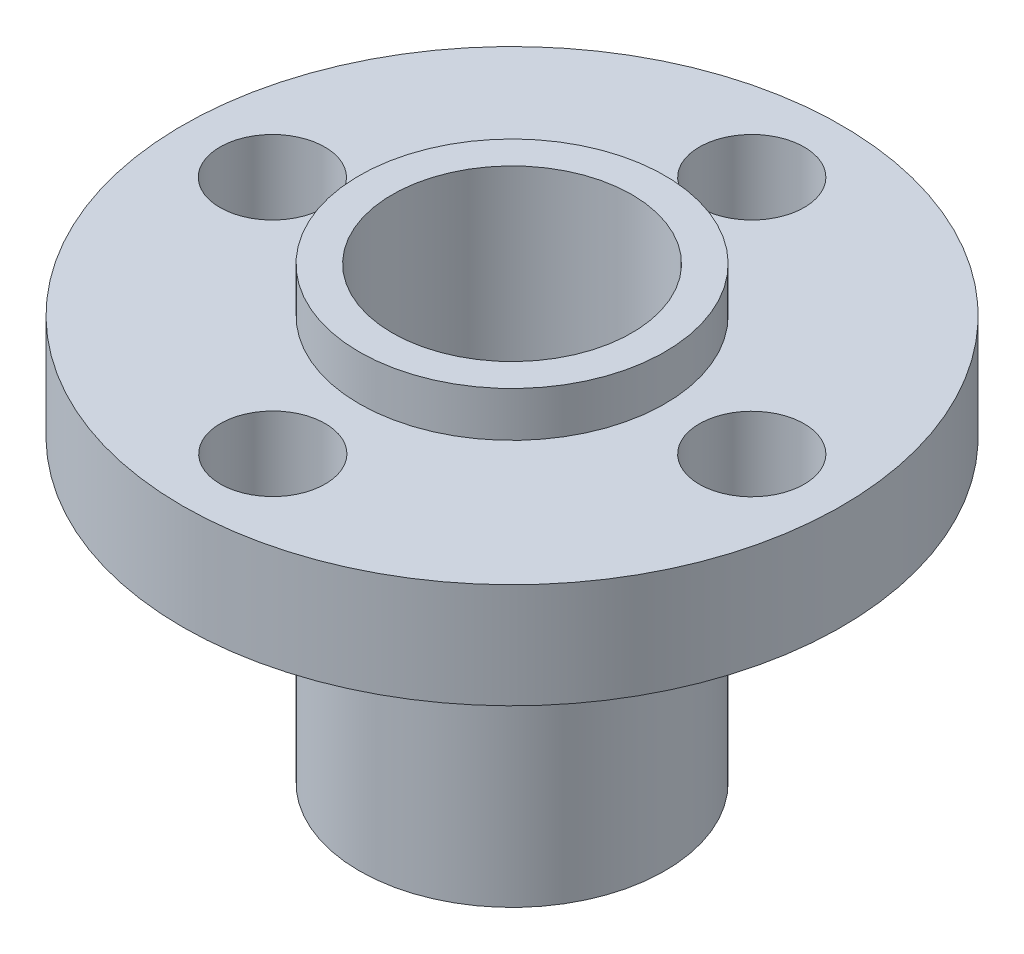
SolidWorks part; units mm, degrees
ref_plane "Front" through (0, 0, 0) normal (0, 0, 1) x (1, 0, 0)
ref_plane "Top" through (0, 0, 0) normal (0, 1, 0) x (1, 0, 0)
ref_plane "Right" through (0, 0, 0) normal (1, 0, 0) x (0, 0, -1)
sketch "草图1" plane through (0, 0, 0) normal (0, 1, 0) x (1, 0, 0)
  circle A0 centre (-9.8904, 3.7185) radius 11
  circle A2 centre (-9.8904, -4.268) radius 1.75
  circle A3 centre (-1.8904, 3.7185) radius 1.75
  circle A4 centre (-9.8904, 11.7185) radius 1.75
  circle A5 centre (-17.8904, 3.7185) radius 1.75
  circle A6 centre (-9.8904, 3.7185) radius 5.1
  circle A7 centre (-9.8904, 3.7185) radius 4
  dimension "D1" = 22
  dimension "D3" = 3.5
  dimension "D4" = 3.5
  dimension "D5" = 3.5
  dimension "D6" = 3.5
  dimension "D7" = 10.2
  dimension "D8" = 8
extrude "凸台-拉伸2" add sketch "草图1" along normal blind 3.5 contours A6 A7 | A0 A6 A5 A4 A3 A2 region at (-20.5793, 0, -3.7185) region at (-14.8462, 0, -3.7185)
extrude "凸台-拉伸3" add sketch "草图1<4>" against normal blind 10 contours A6 A7 region at (-14.8462, 0, -3.7185)
sketch "草图1<4>" plane through (0, 0, 0) normal (0, 1, 0) x (1, 0, 0) same geometry as "草图1"
extrude "凸台-拉伸4" add sketch "草图1<5>" along normal blind 5 contours A6 A7 region at (-14.8462, 0, -3.7185)
sketch "草图1<5>" plane through (0, 0, 0) normal (0, 1, 0) x (1, 0, 0) same geometry as "草图1"
